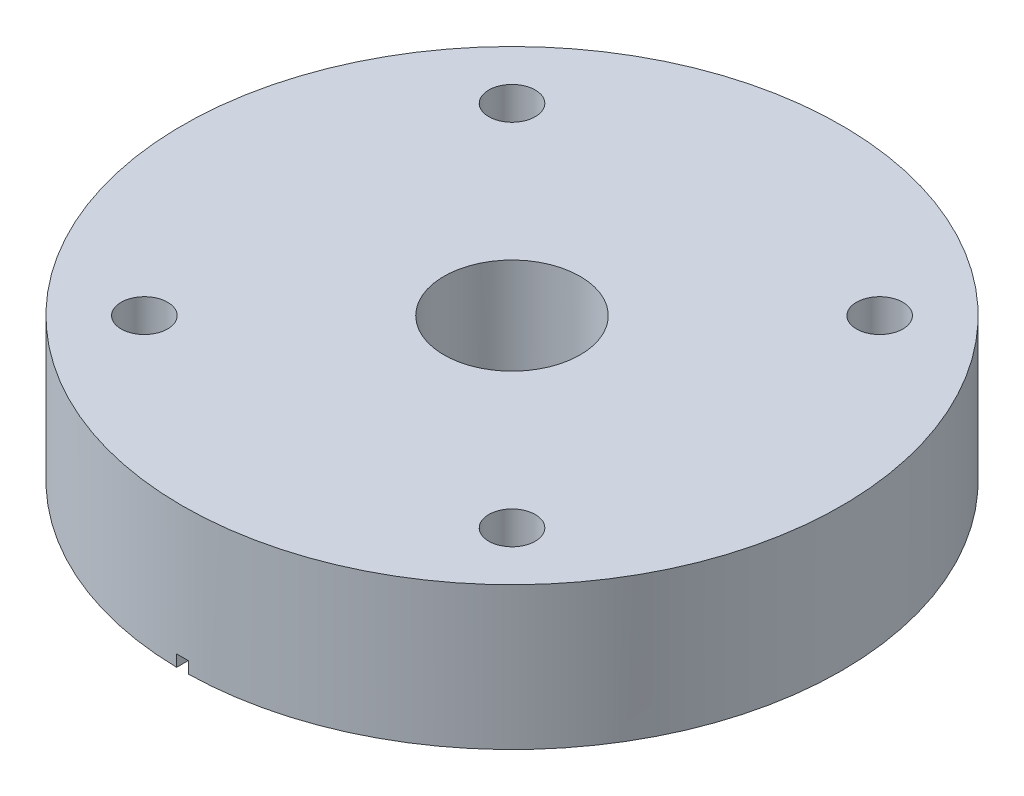
SolidWorks part; units mm, degrees
material "1060 Alloy"
ref_plane "Front" through (0, 0, 0) normal (0, 0, 1) x (1, 0, 0)
ref_plane "Top" through (0, 0, 0) normal (0, 1, 0) x (1, 0, 0)
ref_plane "Right" through (0, 0, 0) normal (1, 0, 0) x (0, 0, -1)
sketch "Sketch1" plane through (0, 0, 0) normal (0, 1, 0) x (1, 0, 0)
  line L0 (0, 0) -> (0, 44.45) construction
  circle A0 centre (-31.4309, 31.4309) radius 3.9688
  circle A1 centre (31.4309, 31.4309) radius 3.9687
  circle A2 centre (31.4309, -31.4309) radius 3.9687
  circle A3 centre (-31.4309, -31.4309) radius 3.9688
  circle A4 centre (0, 0) radius 10.1459
  arc A5 (-24.1039, 40.8157) -> (-40.8157, 24.1039) centre (-31.4309, 31.4309) ccw construction
  arc A6 (40.8157, 24.1039) -> (24.1039, 40.8157) centre (31.4309, 31.4309) ccw construction
  arc A7 (24.1039, -40.8157) -> (40.8157, -24.1039) centre (31.4309, -31.4309) ccw construction
  arc A8 (-40.8157, -24.1039) -> (-24.1039, -40.8157) centre (-31.4309, -31.4309) ccw construction
  arc A9 (-40.2313, 18.9009) -> (-40.2313, -18.9009) centre (0, 0) ccw construction
  arc A10 (-18.9009, -40.2313) -> (18.9009, -40.2313) centre (0, 0) ccw construction
  arc A11 (40.2313, -18.9009) -> (40.2313, 18.9009) centre (0, 0) ccw construction
  arc A12 (-18.9009, 40.2313) -> (-24.1039, 40.8157) centre (-21.027, 44.7568) cw construction
  arc A13 (18.9009, 40.2313) -> (-18.9009, 40.2313) centre (0, 0) ccw construction
  arc A14 (24.1039, 40.8157) -> (18.9009, 40.2313) centre (21.027, 44.7568) cw construction
  arc A15 (40.8157, 24.1039) -> (40.2313, 18.9009) centre (44.7568, 21.027) ccw construction
  arc A16 (40.2313, -18.9009) -> (40.8157, -24.1039) centre (44.7568, -21.027) ccw construction
  arc A17 (24.1039, -40.8157) -> (18.9009, -40.2313) centre (21.027, -44.7568) ccw construction
  arc A18 (-18.9009, -40.2313) -> (-24.1039, -40.8157) centre (-21.027, -44.7568) ccw construction
  arc A19 (-40.2313, -18.9009) -> (-40.8157, -24.1039) centre (-44.7568, -21.027) cw construction
  arc A20 (-40.2313, 18.9009) -> (-40.8157, 24.1039) centre (-44.7568, 21.027) ccw construction
  circle A21 centre (0, 0) radius 56.3562
  point P0 (0, 0)
  point P17 (0, 0)
  point P27 (0, 0)
  dimension "D5" = 7.9375
  dimension "D6" = 20.2918
  dimension "D1" = 5
  dimension "D2" = 11.9062
  dimension "D3" = 44.45
  dimension "D4" = 4
  dimension "D8" = 4
extrude "body and main holes" add sketch "Sketch1" along normal blind 24.4122
sketch "Sketch3" plane through (0, 24.4122, 0) normal (0, -1, 0) x (1, 0, 0)
  circle A0 centre (0, 0) radius 11.6459
  dimension "D1" = 23.2918
extrude "seal bore" cut sketch "Sketch3" along normal blind 22.4122
sketch "Sketch4" plane through (0, 0, 0) normal (0, -1, 0) x (1, 0, 0)
  line L0 (0, 0) -> (0, 44.45) construction
  line L2 (-1, 56.3563) -> (1, 56.3563)
  line L3 (-1, 56.3563) -> (-1, -56.3562)
  line L4 (-1, -56.3562) -> (1, -56.3562)
  line L5 (1, 56.3563) -> (1, -56.3562)
  line L6 (-1, 56.3563) -> (1, -56.3562) construction
  line L7 (-1, -56.3562) -> (1, 56.3563) construction
  circle A2 centre (0, 0) radius 56.3562 construction
  point P6 (0, 0)
  dimension "D1" = 2
extrude "vent slot" cut sketch "Sketch4" against normal blind 2
equation "\"D3@Sketch1\"=\"square plate bolt pattern diameter\"/2"
equation "\"D1@body and main holes\" = \"lower seal plate thickness\""
equation "\"D1@Sketch3\" = \"lower seal OD\""
equation "\"D1@seal bore\" = \"lower seal bore\""
equation "\"D5@Sketch1\"=\"m8 clearance\""
equation "\"D6@Sketch1\" = \"lower seal plate lip ID\""
equation "\"square plate bolt pattern diameter\"= 3.5in"
equation "\"square plate bolt bore\" = \"m8 clearance\""
equation "\"square plate bolt head diameter\" = 13.5mm"
equation "\"motor OD\" = 64mm"
equation "\"m6 clearance\" = 0.234375in 'this is 15/64 bit = 5.95mm, could use 6mm bit, B bit for 6.04mm or 1/4 bit for 6.35mm"
equation "\"m6 tap\" = 5mm   '5mm is appropriate, could use 13/64 or #5,6,7"
equation "\"m6 head bore diameter\" = 11mm  "
equation "\"m6 head bore depth\" = 7mm 'actual is 6mm"
equation "\"m8 clearance\" = 0.3125in 'this is 5/16in for 7.93mm, could use 8mm, O,P, or 21/64"
equation "\"m8 tap\" = 0.265625in  'this is 17/64 for 6.746875mm"
equation "\"m8 head bore diameter\" = 14mm"
equation "\"m8 head bore depth\" = 9mm 'actual is 8mm"
equation "\"lower seal OD\" = .917in  'this is https://www.mcmaster.com/#9281k121/=174001b"
equation "\"lower seal ID\"= .375in"
equation "\"lower seal depth\" = .625in + .218in"
equation "\"lower seal bore\" = \"lower seal depth\" + 1mm"
equation "\"impeller upper clearance\"= .5mm"
equation "\"impeller bottom clearance\"= .5mm"
equation "\"impeller dowel diameter\" = 2mm"
equation "\"impeller shaft bore depth\" = 12mm"
equation "\"impeller shaft bore\" = 8mm"
equation "\"impeller dowel length\" = 2mm*2 + \"impeller shaft bore\""
equation "\"square plate bolt head depth\" = 8mm"
equation "\"lower seal plate lip depth\" = 2mm"
equation "\"lower seal plate lip ID\" = \"lower seal OD\" - 3mm"
equation "\"lower seal plate thickness\" = \"lower seal plate lip depth\" + \"lower seal bore\""
equation "\"shaft coupler section diameter\" = 8mm"
equation "\"shaft bearing stop length\" = 3mm"
equation "\"shaft lower seal section diameter\" = \"lower seal ID\""
equation "\"shaft lower seal section length\" = \"lower seal plate thickness\" + 1mm"
equation "\"shaft impeller section diameter\" = \"impeller shaft bore\""
equation "\"upper seal plate pressure tap diameter\" = .328125in  'this is 21/64 drill for a 1/8 ANPT tap"
equation "\"motor mount post radius\"= ( 3 * \"square plate bolt bore\" ) / 2"
